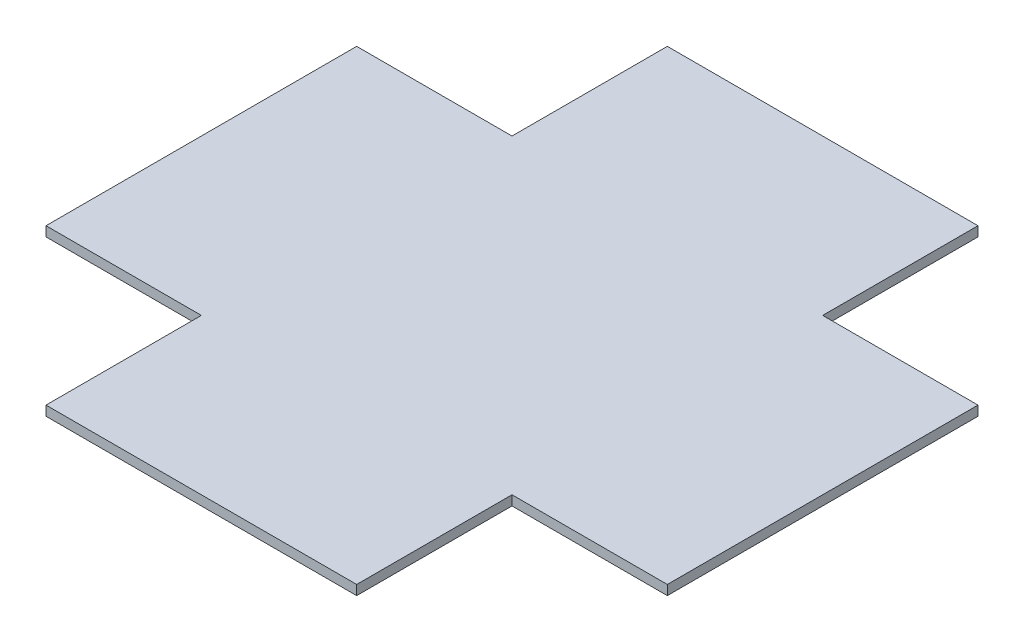
SolidWorks part; units mm, degrees
ref_plane "Front Plane" through (0, 0, 0) normal (0, 0, 1) x (1, 0, 0)
ref_plane "Top Plane" through (0, 0, 0) normal (0, 1, 0) x (1, 0, 0)
ref_plane "Right Plane" through (0, 0, 0) normal (1, 0, 0) x (0, 0, -1)
sketch "Sketch1" plane through (0, 0, 0) normal (0, 1, 0) x (1, 0, 0)
  line L0 (-25.4, 50.8) -> (-25.4, 25.4)
  line L1 (-25.4, 25.4) -> (-50.8, 25.4)
  line L2 (-50.8, 25.4) -> (-50.8, -25.4)
  line L3 (-50.8, -25.4) -> (-25.4, -25.4)
  line L4 (-25.4, -25.4) -> (-25.4, -50.8)
  line L5 (-25.4, -50.8) -> (25.4, -50.8)
  line L6 (25.4, -50.8) -> (25.4, -25.4)
  line L7 (25.4, -25.4) -> (50.8, -25.4)
  line L8 (50.8, -25.4) -> (50.8, 25.4)
  line L9 (50.8, 25.4) -> (25.4, 25.4)
  line L10 (25.4, 25.4) -> (25.4, 50.8)
  line L11 (25.4, 50.8) -> (-25.4, 50.8)
  point P15 (21.3032, 5.7355)
  dimension "D1" = 50.8
  dimension "D2" = 101.6
  dimension "D3" = 50.8
  dimension "D4" = 50.8
extrude "Boss-Extrude1" add sketch "Sketch1" along normal blind 1.5875
